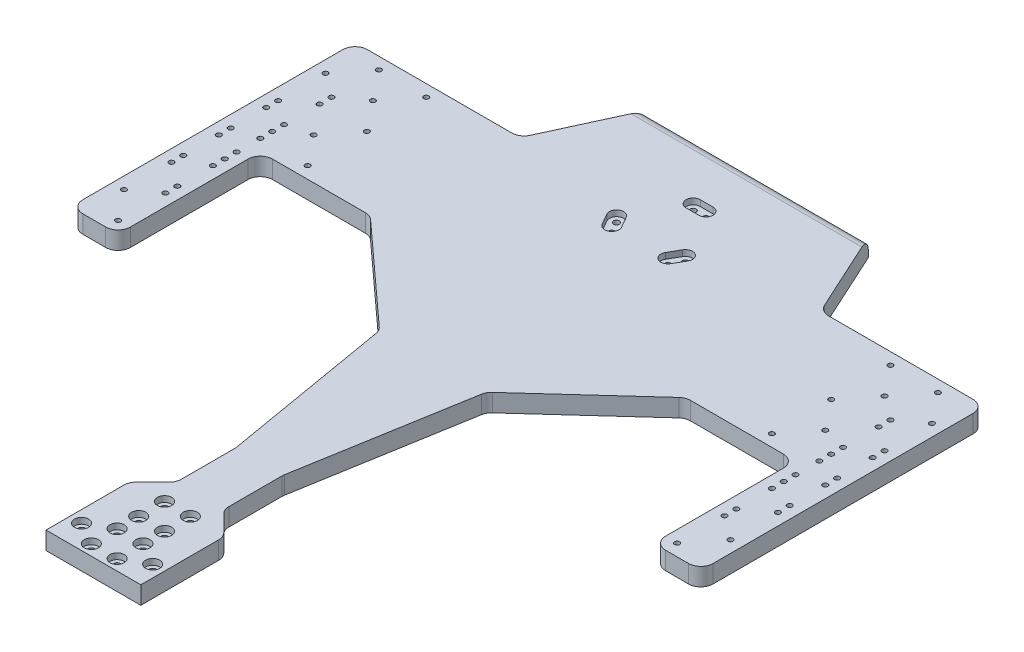
SolidWorks part; units mm, degrees
material "6061-T6 (SS)"
ref_plane "Front Plane" through (0, 0, 0) normal (0, 0, 1) x (1, 0, 0)
ref_plane "Top Plane" through (0, 0, 0) normal (0, 1, 0) x (1, 0, 0)
ref_plane "Right Plane" through (0, 0, 0) normal (1, 0, 0) x (0, 0, -1)
sketch "Sketch1" plane through (0, 0, 0) normal (0, 1, 0) x (1, 0, 0)
  line L0 (-1.4442, 328.045) -> (-2.1645, 328.102)
  line L1 (-2.1645, 328.102) -> (-2.8827, 328.181)
  line L2 (-2.8827, 328.181) -> (-3.598, 328.283)
  line L3 (-3.598, 328.283) -> (-4.3098, 328.407)
  line L4 (-4.3098, 328.407) -> (-5.0173, 328.554)
  line L5 (-5.0173, 328.554) -> (-5.7199, 328.723)
  line L6 (-5.7199, 328.723) -> (-6.4168, 328.913)
  line L7 (-6.4168, 328.913) -> (-7.1074, 329.126)
  line L8 (-7.1074, 329.126) -> (-7.791, 329.36)
  line L9 (-7.791, 329.36) -> (-8.4669, 329.615)
  line L10 (-8.4669, 329.615) -> (-9.1344, 329.892)
  line L11 (-9.1344, 329.892) -> (-9.7929, 330.189)
  line L12 (-9.7929, 330.189) -> (-10.4418, 330.507)
  line L13 (-10.4418, 330.507) -> (-11.0803, 330.845)
  line L14 (-11.0803, 330.845) -> (-11.7079, 331.203)
  line L15 (-11.7079, 331.203) -> (-12.324, 331.58)
  line L16 (-12.324, 331.58) -> (-12.9279, 331.977)
  line L17 (-12.9279, 331.977) -> (-13.5191, 332.393)
  line L18 (-13.5191, 332.393) -> (-14.0968, 332.826)
  line L19 (-14.0968, 332.826) -> (-14.6608, 333.278)
  line L20 (-14.6608, 333.278) -> (-15.2102, 333.747)
  line L21 (-15.2102, 333.747) -> (-15.7446, 334.234)
  line L22 (-15.7446, 334.234) -> (-16.2634, 334.737)
  line L23 (-16.2634, 334.737) -> (-16.7663, 335.255)
  line L24 (-16.7663, 335.255) -> (-17.2525, 335.79)
  line L25 (-17.2525, 335.79) -> (-17.7218, 336.339)
  line L26 (-17.7218, 336.339) -> (-18.1736, 336.903)
  line L27 (-18.1736, 336.903) -> (-18.6074, 337.481)
  line L28 (-18.6074, 337.481) -> (-19.0228, 338.072)
  line L29 (-19.0228, 338.072) -> (-19.4195, 338.676)
  line L30 (-19.4195, 338.676) -> (-19.7971, 339.292)
  line L31 (-19.7971, 339.292) -> (-20.155, 339.92)
  line L32 (-20.155, 339.92) -> (-20.4931, 340.558)
  line L33 (-20.4931, 340.558) -> (-20.811, 341.207)
  line L34 (-20.811, 341.207) -> (-21.1084, 341.866)
  line L35 (-21.1084, 341.866) -> (-21.3849, 342.533)
  line L36 (-21.3849, 342.533) -> (-21.6402, 343.209)
  line L37 (-21.6402, 343.209) -> (-21.8743, 343.893)
  line L38 (-21.8743, 343.893) -> (-22.0867, 344.583)
  line L39 (-22.0867, 344.583) -> (-22.2774, 345.28)
  line L40 (-22.2774, 345.28) -> (-22.4461, 345.983)
  line L41 (-22.4461, 345.983) -> (-22.5926, 346.69)
  line L42 (-22.5926, 346.69) -> (-22.7168, 347.402)
  line L43 (-22.7168, 347.402) -> (-22.8186, 348.117)
  line L44 (-22.8186, 348.117) -> (-22.8979, 348.835)
  line L45 (-22.8979, 348.835) -> (-22.9546, 349.556)
  line L46 (-22.9546, 349.556) -> (-22.9886, 350.278)
  line L47 (-22.9886, 350.278) -> (-23, 351)
  line L48 (-23, 351) -> (-23, 436)
  line L49 (-23, 436) -> (-23.0138, 436.879)
  line L50 (-23.0138, 436.879) -> (-23.0552, 437.758)
  line L51 (-23.0552, 437.758) -> (-23.1243, 438.635)
  line L52 (-23.1243, 438.635) -> (-23.2208, 439.509)
  line L53 (-23.2208, 439.509) -> (-23.3447, 440.38)
  line L54 (-23.3447, 440.38) -> (-23.496, 441.247)
  line L55 (-23.496, 441.247) -> (-23.6743, 442.108)
  line L56 (-23.6743, 442.108) -> (-23.8797, 442.963)
  line L57 (-23.8797, 442.963) -> (-24.1118, 443.812)
  line L58 (-24.1118, 443.812) -> (-24.3704, 444.652)
  line L59 (-24.3704, 444.652) -> (-24.6553, 445.485)
  line L60 (-24.6553, 445.485) -> (-24.9662, 446.307)
  line L61 (-24.9662, 446.307) -> (-25.3029, 447.12)
  line L62 (-25.3029, 447.12) -> (-25.6648, 447.922)
  line L63 (-25.6648, 447.922) -> (-26.0518, 448.712)
  line L64 (-26.0518, 448.712) -> (-26.4634, 449.489)
  line L65 (-26.4634, 449.489) -> (-26.8992, 450.253)
  line L66 (-26.8992, 450.253) -> (-27.3588, 451.003)
  line L67 (-27.3588, 451.003) -> (-27.8417, 451.738)
  line L68 (-27.8417, 451.738) -> (-28.3475, 452.458)
  line L69 (-28.3475, 452.458) -> (-28.8757, 453.161)
  line L70 (-28.8757, 453.161) -> (-29.4256, 453.848)
  line L71 (-29.4256, 453.848) -> (-29.9969, 454.517)
  line L72 (-29.9969, 454.517) -> (-30.5889, 455.167)
  line L73 (-30.5889, 455.167) -> (-31.201, 455.799)
  line L74 (-31.201, 455.799) -> (-31.8327, 456.411)
  line L75 (-31.8327, 456.411) -> (-32.4833, 457.003)
  line L76 (-32.4833, 457.003) -> (-33.1521, 457.574)
  line L77 (-33.1521, 457.574) -> (-33.8386, 458.124)
  line L78 (-33.8386, 458.124) -> (-34.542, 458.652)
  line L79 (-34.542, 458.652) -> (-35.2617, 459.158)
  line L80 (-35.2617, 459.158) -> (-35.9968, 459.641)
  line L81 (-35.9968, 459.641) -> (-36.7468, 460.101)
  line L82 (-36.7468, 460.101) -> (-37.5109, 460.537)
  line L83 (-37.5109, 460.537) -> (-38.2883, 460.948)
  line L84 (-38.2883, 460.948) -> (-39.0782, 461.335)
  line L85 (-39.0782, 461.335) -> (-39.8799, 461.697)
  line L86 (-39.8799, 461.697) -> (-40.6925, 462.034)
  line L87 (-40.6925, 462.034) -> (-41.5153, 462.345)
  line L88 (-41.5153, 462.345) -> (-42.3475, 462.63)
  line L89 (-42.3475, 462.63) -> (-43.1882, 462.888)
  line L90 (-43.1882, 462.888) -> (-44.0367, 463.12)
  line L91 (-44.0367, 463.12) -> (-44.892, 463.326)
  line L92 (-44.892, 463.326) -> (-45.7533, 463.504)
  line L93 (-45.7533, 463.504) -> (-46.6198, 463.655)
  line L94 (-46.6198, 463.655) -> (-47.4907, 463.779)
  line L95 (-47.4907, 463.779) -> (-48.365, 463.876)
  line L96 (-48.365, 463.876) -> (-49.2419, 463.945)
  line L97 (-49.2419, 463.945) -> (-50.1205, 463.986)
  line L98 (-50.1205, 463.986) -> (-51, 464)
  line L99 (-51, 464) -> (-54, 464)
  line L100 (-54, 464) -> (-54.8795, 463.986)
  line L101 (-54.8795, 463.986) -> (-55.7581, 463.945)
  line L102 (-55.7581, 463.945) -> (-56.635, 463.876)
  line L103 (-56.635, 463.876) -> (-57.5093, 463.779)
  line L104 (-57.5093, 463.779) -> (-58.3802, 463.655)
  line L105 (-58.3802, 463.655) -> (-59.2467, 463.504)
  line L106 (-59.2467, 463.504) -> (-60.108, 463.326)
  line L107 (-60.108, 463.326) -> (-60.9633, 463.12)
  line L108 (-60.9633, 463.12) -> (-61.8117, 462.888)
  line L109 (-61.8117, 462.888) -> (-62.6525, 462.63)
  line L110 (-62.6525, 462.63) -> (-63.4846, 462.345)
  line L111 (-63.4846, 462.345) -> (-64.3075, 462.034)
  line L112 (-64.3075, 462.034) -> (-65.1201, 461.697)
  line L113 (-65.1201, 461.697) -> (-65.9218, 461.335)
  line L114 (-65.9218, 461.335) -> (-66.7117, 460.948)
  line L115 (-66.7117, 460.948) -> (-67.4891, 460.537)
  line L116 (-67.4891, 460.537) -> (-68.2532, 460.101)
  line L117 (-68.2532, 460.101) -> (-69.0031, 459.641)
  line L118 (-69.0031, 459.641) -> (-69.7383, 459.158)
  line L119 (-69.7383, 459.158) -> (-70.458, 458.652)
  line L120 (-70.458, 458.652) -> (-71.1614, 458.124)
  line L121 (-71.1614, 458.124) -> (-71.8479, 457.574)
  line L122 (-71.8479, 457.574) -> (-72.5167, 457.003)
  line L123 (-72.5167, 457.003) -> (-73.1673, 456.411)
  line L124 (-73.1673, 456.411) -> (-73.799, 455.799)
  line L125 (-73.799, 455.799) -> (-74.4111, 455.167)
  line L126 (-74.4111, 455.167) -> (-75.0031, 454.517)
  line L127 (-75.0031, 454.517) -> (-75.5744, 453.848)
  line L128 (-75.5744, 453.848) -> (-76.1243, 453.161)
  line L129 (-76.1243, 453.161) -> (-76.6525, 452.458)
  line L130 (-76.6525, 452.458) -> (-77.1582, 451.738)
  line L131 (-77.1582, 451.738) -> (-77.6412, 451.003)
  line L132 (-77.6412, 451.003) -> (-78.1008, 450.253)
  line L133 (-78.1008, 450.253) -> (-78.5366, 449.489)
  line L134 (-78.5366, 449.489) -> (-78.9482, 448.712)
  line L135 (-78.9482, 448.712) -> (-79.3351, 447.922)
  line L136 (-79.3351, 447.922) -> (-79.6971, 447.12)
  line L137 (-79.6971, 447.12) -> (-80.0337, 446.307)
  line L138 (-80.0337, 446.307) -> (-80.3447, 445.485)
  line L139 (-80.3447, 445.485) -> (-80.6296, 444.652)
  line L140 (-80.6296, 444.652) -> (-80.8882, 443.812)
  line L141 (-80.8882, 443.812) -> (-81.1203, 442.963)
  line L142 (-81.1203, 442.963) -> (-81.3257, 442.108)
  line L143 (-81.3257, 442.108) -> (-81.504, 441.247)
  line L144 (-81.504, 441.247) -> (-81.6553, 440.38)
  line L145 (-81.6553, 440.38) -> (-81.7792, 439.509)
  line L146 (-81.7792, 439.509) -> (-81.8757, 438.635)
  line L147 (-81.8757, 438.635) -> (-81.9447, 437.758)
  line L148 (-81.9447, 437.758) -> (-81.9862, 436.879)
  line L149 (-81.9862, 436.879) -> (-82, 436)
  line L150 (-82, 436) -> (-82, 273)
  line L151 (-82, 273) -> (-96, 239)
  line L152 (-96, 239) -> (-114, 205)
  line L153 (-114, 205) -> (-118, 182)
  line L154 (-118, 182) -> (-117, 160)
  line L155 (-117, 160) -> (-113, 147)
  line L156 (-113, 147) -> (-106, 140)
  line L157 (-106, 140) -> (-97, 135)
  line L158 (-97, 135) -> (-76, 120)
  line L159 (-76, 120) -> (-65, 110)
  line L160 (-65, 110) -> (-57, 99)
  line L161 (-57, 99) -> (-54, 93)
  line L162 (-54, 93) -> (-53, 83)
  line L163 (-53, 83) -> (-48, 56)
  line L164 (-48, 56) -> (-38, 29)
  line L165 (-38, 29) -> (-32, 18)
  line L166 (-32, 18) -> (-27, 12)
  line L167 (-27, 12) -> (-19, 7)
  line L168 (-19, 7) -> (-11, 3)
  line L169 (-11, 3) -> (-5, 1)
  line L170 (-5, 1) -> (0, 0)
  line L171 (0, 0) -> (5, 1)
  line L172 (5, 1) -> (11, 3)
  line L173 (11, 3) -> (19, 7)
  line L174 (19, 7) -> (27, 12)
  line L175 (27, 12) -> (32, 18)
  line L176 (32, 18) -> (38, 29)
  line L177 (38, 29) -> (48, 56)
  line L178 (48, 56) -> (53, 83)
  line L179 (53, 83) -> (54, 93)
  line L180 (54, 93) -> (57, 99)
  line L181 (57, 99) -> (65, 110)
  line L182 (65, 110) -> (76, 120)
  line L183 (76, 120) -> (97, 135)
  line L184 (97, 135) -> (106, 140)
  line L185 (106, 140) -> (113, 147)
  line L186 (113, 147) -> (117, 160)
  line L187 (117, 160) -> (118, 182)
  line L188 (118, 182) -> (114, 205)
  line L189 (114, 205) -> (96, 239)
  line L190 (96, 239) -> (82, 273)
  line L191 (82, 273) -> (82, 436)
  line L192 (82, 436) -> (81.9862, 436.879)
  line L193 (81.9862, 436.879) -> (81.9447, 437.758)
  line L194 (81.9447, 437.758) -> (81.8757, 438.635)
  line L195 (81.8757, 438.635) -> (81.7792, 439.509)
  line L196 (81.7792, 439.509) -> (81.6553, 440.38)
  line L197 (81.6553, 440.38) -> (81.504, 441.247)
  line L198 (81.504, 441.247) -> (81.3257, 442.108)
  line L199 (81.3257, 442.108) -> (81.1203, 442.963)
  line L200 (81.1203, 442.963) -> (80.8882, 443.812)
  line L201 (80.8882, 443.812) -> (80.6296, 444.652)
  line L202 (80.6296, 444.652) -> (80.3447, 445.485)
  line L203 (80.3447, 445.485) -> (80.0337, 446.307)
  line L204 (80.0337, 446.307) -> (79.6971, 447.12)
  line L205 (79.6971, 447.12) -> (79.3351, 447.922)
  line L206 (79.3351, 447.922) -> (78.9482, 448.712)
  line L207 (78.9482, 448.712) -> (78.5366, 449.489)
  line L208 (78.5366, 449.489) -> (78.1008, 450.253)
  line L209 (78.1008, 450.253) -> (77.6412, 451.003)
  line L210 (77.6412, 451.003) -> (77.1582, 451.738)
  line L211 (77.1582, 451.738) -> (76.6525, 452.458)
  line L212 (76.6525, 452.458) -> (76.1243, 453.161)
  line L213 (76.1243, 453.161) -> (75.5744, 453.848)
  line L214 (75.5744, 453.848) -> (75.0031, 454.517)
  line L215 (75.0031, 454.517) -> (74.4111, 455.167)
  line L216 (74.4111, 455.167) -> (73.799, 455.799)
  line L217 (73.799, 455.799) -> (73.1673, 456.411)
  line L218 (73.1673, 456.411) -> (72.5167, 457.003)
  line L219 (72.5167, 457.003) -> (71.8479, 457.574)
  line L220 (71.8479, 457.574) -> (71.1614, 458.124)
  line L221 (71.1614, 458.124) -> (70.458, 458.652)
  line L222 (70.458, 458.652) -> (69.7383, 459.158)
  line L223 (69.7383, 459.158) -> (69.0031, 459.641)
  line L224 (69.0031, 459.641) -> (68.2532, 460.101)
  line L225 (68.2532, 460.101) -> (67.4891, 460.537)
  line L226 (67.4891, 460.537) -> (66.7117, 460.948)
  line L227 (66.7117, 460.948) -> (65.9218, 461.335)
  line L228 (65.9218, 461.335) -> (65.1201, 461.697)
  line L229 (65.1201, 461.697) -> (64.3075, 462.034)
  line L230 (64.3075, 462.034) -> (63.4846, 462.345)
  line L231 (63.4846, 462.345) -> (62.6525, 462.63)
  line L232 (62.6525, 462.63) -> (61.8117, 462.888)
  line L233 (61.8117, 462.888) -> (60.9633, 463.12)
  line L234 (60.9633, 463.12) -> (60.108, 463.326)
  line L235 (60.108, 463.326) -> (59.2467, 463.504)
  line L236 (59.2467, 463.504) -> (58.3802, 463.655)
  line L237 (58.3802, 463.655) -> (57.5093, 463.779)
  line L238 (57.5093, 463.779) -> (56.635, 463.876)
  line L239 (56.635, 463.876) -> (55.7581, 463.945)
  line L240 (55.7581, 463.945) -> (54.8795, 463.986)
  line L241 (54.8795, 463.986) -> (54, 464)
  line L242 (54, 464) -> (51, 464)
  line L243 (51, 464) -> (50.1205, 463.986)
  line L244 (50.1205, 463.986) -> (49.2419, 463.945)
  line L245 (49.2419, 463.945) -> (48.365, 463.876)
  line L246 (48.365, 463.876) -> (47.4907, 463.779)
  line L247 (47.4907, 463.779) -> (46.6198, 463.655)
  line L248 (46.6198, 463.655) -> (45.7533, 463.504)
  line L249 (45.7533, 463.504) -> (44.892, 463.326)
  line L250 (44.892, 463.326) -> (44.0367, 463.12)
  line L251 (44.0367, 463.12) -> (43.1882, 462.888)
  line L252 (43.1882, 462.888) -> (42.3475, 462.63)
  line L253 (42.3475, 462.63) -> (41.5153, 462.345)
  line L254 (41.5153, 462.345) -> (40.6925, 462.034)
  line L255 (40.6925, 462.034) -> (39.8799, 461.697)
  line L256 (39.8799, 461.697) -> (39.0782, 461.335)
  line L257 (39.0782, 461.335) -> (38.2883, 460.948)
  line L258 (38.2883, 460.948) -> (37.5109, 460.537)
  line L259 (37.5109, 460.537) -> (36.7468, 460.101)
  line L260 (36.7468, 460.101) -> (35.9968, 459.641)
  line L261 (35.9968, 459.641) -> (35.2617, 459.158)
  line L262 (35.2617, 459.158) -> (34.542, 458.652)
  line L263 (34.542, 458.652) -> (33.8386, 458.124)
  line L264 (33.8386, 458.124) -> (33.1521, 457.574)
  line L265 (33.1521, 457.574) -> (32.4833, 457.003)
  line L266 (32.4833, 457.003) -> (31.8327, 456.411)
  line L267 (31.8327, 456.411) -> (31.201, 455.799)
  line L268 (31.201, 455.799) -> (30.5889, 455.167)
  line L269 (30.5889, 455.167) -> (29.9969, 454.517)
  line L270 (29.9969, 454.517) -> (29.4256, 453.848)
  line L271 (29.4256, 453.848) -> (28.8757, 453.161)
  line L272 (28.8757, 453.161) -> (28.3475, 452.458)
  line L273 (28.3475, 452.458) -> (27.8417, 451.738)
  line L274 (27.8417, 451.738) -> (27.3588, 451.003)
  line L275 (27.3588, 451.003) -> (26.8992, 450.253)
  line L276 (26.8992, 450.253) -> (26.4634, 449.489)
  line L277 (26.4634, 449.489) -> (26.0518, 448.712)
  line L278 (26.0518, 448.712) -> (25.6648, 447.922)
  line L279 (25.6648, 447.922) -> (25.3029, 447.12)
  line L280 (25.3029, 447.12) -> (24.9662, 446.307)
  line L281 (24.9662, 446.307) -> (24.6553, 445.485)
  line L282 (24.6553, 445.485) -> (24.3704, 444.652)
  line L283 (24.3704, 444.652) -> (24.1118, 443.812)
  line L284 (24.1118, 443.812) -> (23.8797, 442.963)
  line L285 (23.8797, 442.963) -> (23.6743, 442.108)
  line L286 (23.6743, 442.108) -> (23.496, 441.247)
  line L287 (23.496, 441.247) -> (23.3447, 440.38)
  line L288 (23.3447, 440.38) -> (23.2208, 439.509)
  line L289 (23.2208, 439.509) -> (23.1243, 438.635)
  line L290 (23.1243, 438.635) -> (23.0552, 437.758)
  line L291 (23.0552, 437.758) -> (23.0138, 436.879)
  line L292 (23.0138, 436.879) -> (23, 436)
  line L293 (23, 436) -> (23, 351)
  line L294 (23, 351) -> (22.9886, 350.278)
  line L295 (22.9886, 350.278) -> (22.9546, 349.556)
  line L296 (22.9546, 349.556) -> (22.8979, 348.835)
  line L297 (22.8979, 348.835) -> (22.8186, 348.117)
  line L298 (22.8186, 348.117) -> (22.7168, 347.402)
  line L299 (22.7168, 347.402) -> (22.5926, 346.69)
  line L300 (22.5926, 346.69) -> (22.4461, 345.983)
  line L301 (22.4461, 345.983) -> (22.2774, 345.28)
  line L302 (22.2774, 345.28) -> (22.0867, 344.583)
  line L303 (22.0867, 344.583) -> (21.8743, 343.893)
  line L304 (21.8743, 343.893) -> (21.6402, 343.209)
  line L305 (21.6402, 343.209) -> (21.3849, 342.533)
  line L306 (21.3849, 342.533) -> (21.1084, 341.866)
  line L307 (21.1084, 341.866) -> (20.811, 341.207)
  line L308 (20.811, 341.207) -> (20.4931, 340.558)
  line L309 (20.4931, 340.558) -> (20.155, 339.92)
  line L310 (20.155, 339.92) -> (19.7971, 339.292)
  line L311 (19.7971, 339.292) -> (19.4195, 338.676)
  line L312 (19.4195, 338.676) -> (19.0228, 338.072)
  line L313 (19.0228, 338.072) -> (18.6074, 337.481)
  line L314 (18.6074, 337.481) -> (18.1736, 336.903)
  line L315 (18.1736, 336.903) -> (17.7218, 336.339)
  line L316 (17.7218, 336.339) -> (17.2525, 335.79)
  line L317 (17.2525, 335.79) -> (16.7663, 335.255)
  line L318 (16.7663, 335.255) -> (16.2634, 334.737)
  line L319 (16.2634, 334.737) -> (15.7446, 334.234)
  line L320 (15.7446, 334.234) -> (15.2102, 333.747)
  line L321 (15.2102, 333.747) -> (14.6608, 333.278)
  line L322 (14.6608, 333.278) -> (14.0968, 332.826)
  line L323 (14.0968, 332.826) -> (13.5191, 332.393)
  line L324 (13.5191, 332.393) -> (12.9279, 331.977)
  line L325 (12.9279, 331.977) -> (12.324, 331.58)
  line L326 (12.324, 331.58) -> (11.7079, 331.203)
  line L327 (11.7079, 331.203) -> (11.0803, 330.845)
  line L328 (11.0803, 330.845) -> (10.4418, 330.507)
  line L329 (10.4418, 330.507) -> (9.7929, 330.189)
  line L330 (9.7929, 330.189) -> (9.1344, 329.892)
  line L331 (9.1344, 329.892) -> (8.4669, 329.615)
  line L332 (8.4669, 329.615) -> (7.791, 329.36)
  line L333 (7.791, 329.36) -> (7.1074, 329.126)
  line L334 (7.1074, 329.126) -> (6.4168, 328.913)
  line L335 (6.4168, 328.913) -> (5.7199, 328.723)
  line L336 (5.7199, 328.723) -> (5.0173, 328.554)
  line L337 (5.0173, 328.554) -> (4.3098, 328.407)
  line L338 (4.3098, 328.407) -> (3.598, 328.283)
  line L339 (3.598, 328.283) -> (2.8827, 328.181)
  line L340 (2.8827, 328.181) -> (2.1645, 328.102)
  line L341 (2.1645, 328.102) -> (1.4442, 328.045)
  line L342 (1.4442, 328.045) -> (0.7224, 328.011)
  line L343 (0.7224, 328.011) -> (0, 328)
  line L344 (0, 328) -> (-0.7224, 328.011)
  line L345 (-0.7224, 328.011) -> (-1.4442, 328.045)
extrude "Boss-Extrude1" add sketch "Sketch1" along normal blind 9.525
ref_axis "Axis1" through (-117, 9.525, -160) along (1, 0, 0)
ref_plane "plane_aft_cg" through (0, 0, -160) normal (0, 0, 1) x (1, 0, 0)
ref_axis "Axis2" through (0, 9.525, -328) along (0, 0, 1)
ref_plane "Plane3" through (0, 0, 0) normal (-1, 0, 0) x (0, 0, 1)
ref_axis "Axis3" through (-82, 9.525, -273) along (1, 0, 0)
ref_plane "plane_fore_cg" through (0, 0, -273) normal (0, 0, 1) x (1, 0, 0)
ref_plane "plane_design_cg" through (0, 0, -216.5) normal (0, 0, 1) x (1, 0, 0)
sketch "Sketch2" plane through (0, 0, 0) normal (0, -1, 0) x (1, 0, 0)
  line L0 (0, 0) -> (0, 14.1955) construction
  line L1 (0, 18.0958) -> (0, -18.0958) construction
  line L2 (-7.9998, 0) -> (16.638, 0) construction
  line L4 (-25.4, -38.1) -> (25.4, -38.1)
  line L5 (-25.4, -38.1) -> (-25.4, 38.1)
  line L6 (-25.4, 38.1) -> (25.4, 38.1)
  line L7 (25.4, -38.1) -> (25.4, 38.1)
  dimension "D1" = 25.4
  dimension "D2" = 50.8
  dimension "D3" = 38.1
  dimension "D4" = 38.1
extrude "perineum_support" add sketch "Sketch2" against normal blind 9.525
sketch "Sketch3" plane through (0, 9.525, 0) normal (0, 1, 0) x (1, 0, 0)
  line L1 (-25.4, -38.1) -> (25.4, -38.1)
  line L2 (-25.4, -38.1) -> (-25.4, -88.9)
  line L3 (-25.4, -88.9) -> (25.4, -88.9)
  line L4 (25.4, -38.1) -> (25.4, -88.9)
  dimension "D1" = 50.8
extrude "rail_wheel_mount" add sketch "Sketch3" against normal blind 9.525
sketch "Sketch4" plane through (0, 9.525, 0) normal (0, 1, 0) x (1, 0, 0)
  line L0 (-108.3287, 216.5) -> (107.5479, 216.5) construction
  line L1 (-21.7004, 216.5) -> (21.7004, 216.5) construction
  line L2 (0, 328.4728) -> (0, -157.3405) construction
  line L3 (0, 18.0958) -> (0, -18.0958) construction
  line L4 (0, 328) -> (0, 0) construction
  line L5 (0, 216.5) -> (5.4326, 247.3096) construction
  line L6 (0, 216.5) -> (-5.4326, 247.3096) construction
  circle A2 centre (0, 216.5) radius 19.62 construction
  circle A3 centre (3.407, 235.8219) radius 1.575
  circle A4 centre (-3.407, 235.8219) radius 1.575
  circle A9 centre (18.4368, 209.7896) radius 1.575
  circle A10 centre (15.0298, 203.8885) radius 1.575
  circle A11 centre (-15.0298, 203.8885) radius 1.575
  circle A12 centre (-18.4368, 209.7896) radius 1.575
  point P10 (0, 216.5)
  point P30 (0, 216.5)
  point P31 (0, 216.5)
  dimension "D1" = 39.24
  dimension "D3" = 3.15
  dimension "D4" = 3.15
  dimension "D2" = 10
  dimension "D5" = 3
sketch "Sketch6" plane through (0, 9.525, 0) normal (0, 1, 0) x (1, 0, 0)
  line L0 (0, 327.3919) -> (0, -88.9) construction
  line L1 (0, 18.0958) -> (0, -18.0958) construction
  line L2 (0, 328) -> (0, 0) construction
  line L3 (-25.4, -88.9) -> (25.4, -88.9) construction
  line L4 (-165.4829, 182) -> (156.4147, 182) construction
  line L5 (-118, 205.5638) -> (-118, 134.8649) construction
  line L7 (-143.4, 220.1) -> (143.4, 220.1)
  line L8 (118, 209.6903) -> (118, 142.7358) construction
  line L9 (-143.4, 220.1) -> (-143.4, 143.9)
  line L10 (-143.4, 143.9) -> (143.4, 143.9)
  line L11 (143.4, 220.1) -> (143.4, 143.9)
  dimension "D1" = 25.4
  dimension "D2" = 25.4
  dimension "D3" = 38.1
  dimension "D4" = 38.1
extrude "wheelbase" add sketch "Sketch6" against normal blind 9.525
extrude "thru_hole_FT_sensor" cut sketch "Sketch4" against normal blind 9.525
sketch "Sketch8" plane through (0, 9.525, 0) normal (0, 1, 0) x (1, 0, 0)
  line L0 (-3.407, 239.6319) -> (3.407, 239.6319)
  line L1 (3.407, 232.0119) -> (-3.407, 232.0119)
  line L2 (21.7363, 207.8846) -> (18.3293, 201.9835)
  line L3 (11.7302, 205.7935) -> (15.1372, 211.6946)
  line L4 (-18.3293, 201.9835) -> (-21.7363, 207.8846)
  line L5 (-15.1372, 211.6946) -> (-11.7302, 205.7935)
  arc A0 (3.407, 232.0119) -> (3.407, 239.6319) centre (3.407, 235.8219) ccw
  arc A1 (-3.407, 239.6319) -> (-3.407, 232.0119) centre (-3.407, 235.8219) ccw
  arc A2 (21.7363, 207.8846) -> (15.1372, 211.6946) centre (18.4368, 209.7896) ccw
  arc A3 (11.7302, 205.7935) -> (18.3293, 201.9835) centre (15.0298, 203.8885) ccw
  arc A4 (-18.3293, 201.9835) -> (-11.7302, 205.7935) centre (-15.0298, 203.8885) ccw
  arc A5 (-15.1372, 211.6946) -> (-21.7363, 207.8846) centre (-18.4368, 209.7896) ccw
  point P1 (0, 216.5)
  point P25 (0, 216.5)
  dimension "D1" = 7.62
  dimension "D2" = 7.62
  dimension "D3" = 3
extrude "counterbore_FT_sensor" cut sketch "Sketch8" against normal blind 3.175
sketch "Sketch9" plane through (0, 0, 0) normal (0, -1, 0) x (1, 0, 0)
  line L0 (-143.4, -123.6733) -> (-143.4, -238.972) construction
  line L1 (-130.7, -119.4378) -> (-130.7, -247.6783) construction
  line L2 (-171.894, -182) -> (-75.8901, -182) construction
  line L3 (0, 157.3405) -> (0, -499.3009) construction
  line L4 (-106.0059, -220.1) -> (-143.4, -220.1) construction
  line L5 (-143.4, -143.9) -> (-109.9, -143.9) construction
  circle A2 centre (-137.05, -166.125) radius 1.3525
  circle A3 centre (-124.35, -150.25) radius 1.3525
  circle A4 centre (-124.35, -182) radius 1.3525
  circle A5 centre (-124.35, -213.75) radius 1.3525
  circle A6 centre (-137.05, -197.875) radius 1.3525
  circle A7 centre (137.05, -197.875) radius 1.3525
  circle A8 centre (124.35, -213.75) radius 1.3525
  circle A9 centre (124.35, -182) radius 1.3525
  circle A10 centre (124.35, -150.25) radius 1.3525
  circle A11 centre (137.05, -166.125) radius 1.3525
  dimension "D4" = 2.7051
  dimension "D8" = 2.7051
  dimension "D9" = 2.7051
  dimension "D1" = 12.7
  dimension "D2" = 38.1
  dimension "D3" = 15.875
  dimension "D7" = 6.35
  dimension "D10" = 31.75
  dimension "D11" = 6.35
  dimension "D12" = 6.35
extrude "drive_mt_holes" cut sketch "Sketch9" against normal blind 9.525
sketch "Sketch10" plane through (0, 0, 0) normal (0, -1, 0) x (1, 0, 0)
  line L0 (-91.3183, 38.1) -> (70.9855, 38.1) construction
  line L1 (-25.4, 88.9) -> (25.4, 88.9) construction
  line L2 (-66.5601, 63.5) -> (69.0599, 63.5) construction
  line L3 (-47.6939, 50.8) -> (48.5015, 50.8) construction
  line L4 (0, -328.4728) -> (0, 157.3405) construction
  line L5 (-37.3667, 76.2) -> (53.9123, 76.2) construction
  circle A0 centre (6.9152, 57.7152) radius 1.8288
  circle A1 centre (6.9152, 43.8848) radius 1.8288
  circle A2 centre (-6.9151, 43.8848) radius 1.8288
  circle A3 centre (-6.9151, 57.7151) radius 1.8288
  circle A4 centre (-6.9151, 83.1152) radius 1.8288
  circle A5 centre (6.9152, 83.1152) radius 1.8288
  circle A6 centre (6.9152, 69.2849) radius 1.8288
  circle A7 centre (-6.9151, 69.2849) radius 1.8288
  circle A8 centre (-19.05, 76.2) radius 1.8288
  circle A9 centre (19.05, 76.2) radius 1.8288
  point P12 (0, 50.8)
  point P22 (0, 50.8)
  dimension "D4" = 3.6576
  dimension "D5" = 6.9151
  dimension "D9" = 3.6576
  dimension "D10" = 3.6576
  dimension "D1" = 50.8
  dimension "D2" = 25.4
  dimension "D3" = 12.7
  dimension "D6" = 6.9151
  dimension "D8" = 12.7
  dimension "D11" = 19.05
  dimension "D12" = 19.05
  dimension "D7" = 4
extrude "thru_holes_rail_wheel_mount" cut sketch "Sketch10" against normal blind 9.525
sketch "Sketch11" plane through (0, 9.525, 0) normal (0, 1, 0) x (1, 0, 0)
  circle A0 centre (-6.9151, -43.8848) radius 3.81
  circle A1 centre (6.9152, -43.8848) radius 3.81
  circle A2 centre (-19.05, -76.2) radius 3.81
  circle A3 centre (19.05, -76.2) radius 3.81
  circle A4 centre (6.9152, -57.7152) radius 3.81
  circle A5 centre (-6.9151, -57.7151) radius 3.81
  circle A6 centre (-6.9151, -69.2849) radius 3.81
  circle A7 centre (-6.9151, -83.1152) radius 3.81
  circle A8 centre (6.9152, -69.2849) radius 3.81
  circle A9 centre (6.9152, -83.1152) radius 3.81
  dimension "D1" = 7.62
  dimension "D2" = 7.62
  dimension "D3" = 7.62
  dimension "D4" = 7.62
  dimension "D5" = 7.62
  dimension "D6" = 7.62
  dimension "D7" = 7.62
  dimension "D8" = 7.62
  dimension "D9" = 7.62
  dimension "D10" = 7.62
extrude "counterbore_rail_wheel_mount" cut sketch "Sketch11" against normal blind 3.175
sketch "Sketch12" plane through (0, 9.525, 0) normal (0, 1, 0) x (1, 0, 0)
  line L1 (-156.2521, 572.1) -> (172.1218, 572.1)
  line L2 (-156.2521, 572.1) -> (-156.2521, 267.3)
  line L3 (-156.2521, 267.3) -> (172.1218, 267.3)
  line L4 (172.1218, 572.1) -> (172.1218, 267.3)
  circle A0 centre (0, 216.5) radius 19.62 construction
  dimension "D1" = 50.8
  dimension "D2" = 304.8
extrude "remove_face_support" cut sketch "Sketch12" against normal blind 9525
ref_axis "Axis4" through (25.4, 0, -11) along (0, 0, 1)
ref_axis "Axis5" through (143.4, 0, 102.7796) along (0, 0, -1)
ref_axis "Axis6" through (-25.4, 0, 88.9) along (1, 0, 0)
ref_point "Point1"
sketch "Sketch13" plane through (0, 0, 0) normal (0, -1, 0) x (1, 0, 0)
  line L9 (0, 18.0958) -> (0, -18.0958) construction
  line L10 (143.4, -220.1) -> (168.8, -220.1)
  line L11 (143.4, -220.1) -> (143.4, -67.7)
  line L12 (143.4, -67.7) -> (168.8, -67.7)
  line L13 (168.8, -220.1) -> (168.8, -67.7)
  line L14 (-168.8, -220.1) -> (-168.8, -67.7)
  line L15 (-143.4, -67.7) -> (-168.8, -67.7)
  line L16 (-143.4, -220.1) -> (-143.4, -67.7)
  line L17 (-143.4, -220.1) -> (-168.8, -220.1)
  dimension "D1" = 152.4
  dimension "D2" = 25.4
extrude "extended_drive_mount" add sketch "Sketch13" against normal blind 9.525
sketch "Sketch14" plane through (0, 9.525, 0) normal (0, 1, 0) x (1, 0, 0)
  line L0 (-156.1, 67.7) -> (-156.1, 237.0078) construction
  line L1 (-143.4, 67.7) -> (-168.8, 67.7) construction
  line L2 (-243.2313, 156.6) -> (-123.7823, 156.6) construction
  line L3 (-106.0059, 220.1) -> (-168.8, 220.1) construction
  line L4 (0, 18.0958) -> (0, -18.0958) construction
  circle A0 centre (-162.45, 140.725) radius 1.3525
  circle A3 centre (-149.75, 124.85) radius 1.3525
  circle A4 centre (-149.75, 188.35) radius 1.3525
  circle A5 centre (-162.45, 172.475) radius 1.3525
  circle A6 centre (162.45, 172.475) radius 1.3525
  circle A7 centre (149.75, 188.35) radius 1.3525
  circle A8 centre (149.75, 124.85) radius 1.3525
  circle A10 centre (162.45, 140.725) radius 1.3525
  circle A11 centre (-149.75, 156.6) radius 1.3525
  circle A12 centre (149.75, 156.6) radius 1.3525
  point P32 (-156.1, 152.3539)
  dimension "D2" = 2.7051
  dimension "D3" = 2.7051
  dimension "D9" = 2.7051
  dimension "D1" = 63.5
  dimension "D5" = 6.35
  dimension "D6" = 6.35
  dimension "D7" = 15.875
  dimension "D8" = 31.75
  dimension "D10" = 6.35
extrude "drive_mt_holes_1in_off" cut sketch "Sketch14" against normal blind 9.525
sketch "Sketch15" plane through (0, 9.525, 0) normal (0, 1, 0) x (1, 0, 0)
  line L0 (-156.1, 67.7) -> (-156.1, 258.0694) construction
  line L1 (-143.4, 67.7) -> (-168.8, 67.7) construction
  line L2 (-112.5741, 131.2) -> (-234.525, 131.2) construction
  line L3 (-106.0059, 220.1) -> (-168.8, 220.1) construction
  line L4 (0, 18.0958) -> (0, -18.0958) construction
  circle A1 centre (-162.45, 115.325) radius 1.3526
  circle A2 centre (-149.75, 99.45) radius 1.3526
  circle A3 centre (-149.75, 162.95) radius 1.3526
  circle A4 centre (-162.45, 147.075) radius 1.3526
  circle A5 centre (162.45, 147.075) radius 1.3526
  circle A6 centre (149.75, 162.95) radius 1.3526
  circle A7 centre (149.75, 99.45) radius 1.3526
  circle A8 centre (162.45, 115.325) radius 1.3526
  circle A10 centre (-149.75, 131.2) radius 1.3525
  circle A11 centre (149.75, 131.2) radius 1.3525
  dimension "D6" = 2.7051
  dimension "D7" = 2.7051
  dimension "D8" = 2.7051
  dimension "D1" = 88.9
  dimension "D2" = 6.35
  dimension "D3" = 6.35
  dimension "D4" = 15.875
  dimension "D5" = 31.75
  dimension "D9" = 6.35
extrude "drive_mt_holes_2in_off" cut sketch "Sketch15" against normal blind 9.525
sketch "Sketch16" plane through (0, 9.525, 0) normal (0, 1, 0) x (1, 0, 0)
  line L0 (-156.1, 67.7) -> (-156.1, 257.16) construction
  line L1 (-143.4, 67.7) -> (-168.8, 67.7) construction
  line L2 (-118.4098, 105.8) -> (-220.5416, 105.8) construction
  line L3 (-106.0059, 220.1) -> (-168.8, 220.1) construction
  line L4 (0, 18.0958) -> (0, -18.0958) construction
  circle A1 centre (-162.45, 89.925) radius 1.3526
  circle A2 centre (-149.75, 74.05) radius 1.3526
  circle A3 centre (-149.75, 137.55) radius 1.3526
  circle A4 centre (-162.45, 121.675) radius 1.3526
  circle A5 centre (162.45, 121.675) radius 1.3526
  circle A6 centre (149.75, 137.55) radius 1.3526
  circle A7 centre (149.75, 74.05) radius 1.3526
  circle A8 centre (162.45, 89.925) radius 1.3526
  circle A10 centre (-149.75, 105.8) radius 1.3526
  circle A11 centre (149.75, 105.8) radius 1.3526
  dimension "D2" = 2.7051
  dimension "D3" = 2.7051
  dimension "D4" = 2.7051
  dimension "D1" = 114.3
  dimension "D5" = 6.35
  dimension "D6" = 6.35
  dimension "D7" = 15.875
  dimension "D8" = 31.75
  dimension "D9" = 6.35
extrude "drive_mt_holes_3in_off" cut sketch "Sketch16" against normal blind 9.525
sketch "Sketch19" plane through (0, 9.525, 0) normal (0, 1, 0) x (1, 0, 0)
  line L0 (109.9, 143.9) -> (84.5, 143.9)
  line L6 (84.5, 143.9) -> (28.6, 93)
  line L8 (109.9, 143.9) -> (109.9, 0)
  line L9 (109.9, 0) -> (12.7, 0)
  line L10 (12.7, 0) -> (28.6, 93)
  line L11 (25.4, 11) -> (25.4, -88.9) construction
  line L12 (0, 18.0958) -> (0, -18.0958) construction
  line L13 (-12.7, 0) -> (-28.6, 93)
  line L14 (-109.9, 0) -> (-12.7, 0)
  line L15 (-109.9, 143.9) -> (-109.9, 0)
  line L16 (-84.5, 143.9) -> (-28.6, 93)
  line L17 (-109.9, 143.9) -> (-84.5, 143.9)
  dimension "D1" = 12.7
  dimension "D2" = 25.4
  dimension "D3" = 25.4
extrude "trim_rear_chassis" cut sketch "Sketch19" against normal blind 9.525
sketch "Sketch20" plane through (0, 9.525, 0) normal (0, 1, 0) x (1, 0, 0)
  line L0 (106.0059, 220.1) -> (80.6059, 220.1)
  line L1 (80.6059, 220.1) -> (58.9471, 267.3)
  line L2 (-84.3471, 267.3) -> (84.3471, 267.3) construction
  line L3 (58.9471, 267.3) -> (118.35, 267.3)
  line L4 (118.35, 267.3) -> (118.35, 220.1)
  line L5 (168.8, 220.1) -> (106.0059, 220.1) construction
  line L6 (118.35, 220.1) -> (106.0059, 220.1)
  line L7 (0, 18.0958) -> (0, -18.0958) construction
  line L8 (-118.35, 220.1) -> (-106.0059, 220.1)
  line L9 (-118.35, 267.3) -> (-118.35, 220.1)
  line L10 (-58.9471, 267.3) -> (-118.35, 267.3)
  line L11 (-80.6059, 220.1) -> (-58.9471, 267.3)
  line L12 (-106.0059, 220.1) -> (-80.6059, 220.1)
  dimension "D1" = 25.4
  dimension "D2" = 25.4
extrude "trim_forward_chassis" cut sketch "Sketch20" against normal blind 9.525
sketch "Sketch21" plane through (0, 9.525, 0) normal (0, 1, 0) x (1, 0, 0)
  line L0 (12.7, 0) -> (12.7, -31.75)
  line L1 (12.7, -31.75) -> (25.4, -44.45)
  line L2 (25.4, 11) -> (25.4, -88.9) construction
  line L3 (25.4, -44.45) -> (25.4, 0)
  line L4 (25.4, 0) -> (12.7, 0)
  line L5 (12.7, -31.75) -> (42.6161, -31.75) construction
  line L6 (0, 18.0958) -> (0, -18.0958) construction
  line L7 (-25.4, 0) -> (-12.7, 0)
  line L8 (-25.4, -44.45) -> (-25.4, 0)
  line L9 (-12.7, -31.75) -> (-25.4, -44.45)
  line L10 (-12.7, 0) -> (-12.7, -31.75)
  dimension "D1" = 31.75
  dimension "D2" = 45
extrude "trim_tail_wheel_mt" cut sketch "Sketch21" against normal blind 9.525
fillet "fillet_chassis" radius 6.604 20 edges at (-25.4, 4.7625, 44.45) (-12.7, 4.7625, 31.75) (-12.7, 4.7625, 0) (-28.6, 4.7625, -93) (-84.5, 4.7625, -143.9) (-143.4, 4.7625, -143.9) (-143.4, 4.7625, -67.7) (-168.8, 4.7625, -67.7) (-168.8, 4.7625, -220.1) (-80.6059, 4.7625, -220.1) (80.6059, 4.7625, -220.1) (168.8, 4.7625, -220.1) (168.8, 4.7625, -67.7) (143.4, 4.7625, -67.7) (143.4, 4.7625, -143.9) (84.5, 4.7625, -143.9) (28.6, 4.7625, -93) (12.7, 4.7625, 0) (12.7, 4.7625, 31.75) (25.4, 4.7625, 44.45)
fillet "fillet_front" radius 6.35 1 edges at (0, 9.525, -267.3)
sketch "Sketch23" plane through (0, 0, 0) normal (0, -1, 0) x (1, 0, 0)
  line L0 (-156.1, -67.7) -> (-156.1, -251.6371) construction
  line L1 (-150.004, -67.7) -> (-162.196, -67.7) construction
  line L2 (-272.1331, -182) -> (-55.8992, -182) construction
  line L3 (-84.8416, -220.1) -> (-162.196, -220.1) construction
  line L4 (0, 18.0958) -> (0, -18.0958) construction
  circle A0 centre (-149.75, -182) radius 1.3525
  circle A1 centre (-162.45, -166.125) radius 1.3525
  circle A2 centre (-149.75, -150.25) radius 1.3525
  circle A3 centre (-149.75, -213.75) radius 1.3525
  circle A4 centre (-162.45, -197.875) radius 1.3525
  circle A5 centre (149.75, -182) radius 1.3525
  circle A6 centre (162.45, -197.875) radius 1.3525
  circle A7 centre (149.75, -213.75) radius 1.3525
  circle A8 centre (162.45, -166.125) radius 1.3525
  circle A9 centre (149.75, -150.25) radius 1.3525
  dimension "D2" = 2.7051
  dimension "D3" = 2.7051
  dimension "D4" = 2.7051
  dimension "D1" = 38.1
  dimension "D5" = 15.875
  dimension "D6" = 31.75
  dimension "D7" = 6.35
  dimension "D8" = 6.35
  dimension "D9" = 6.35
extrude "drive_mt_holes_0in_off" cut sketch "Sketch23" against normal blind 12.7
